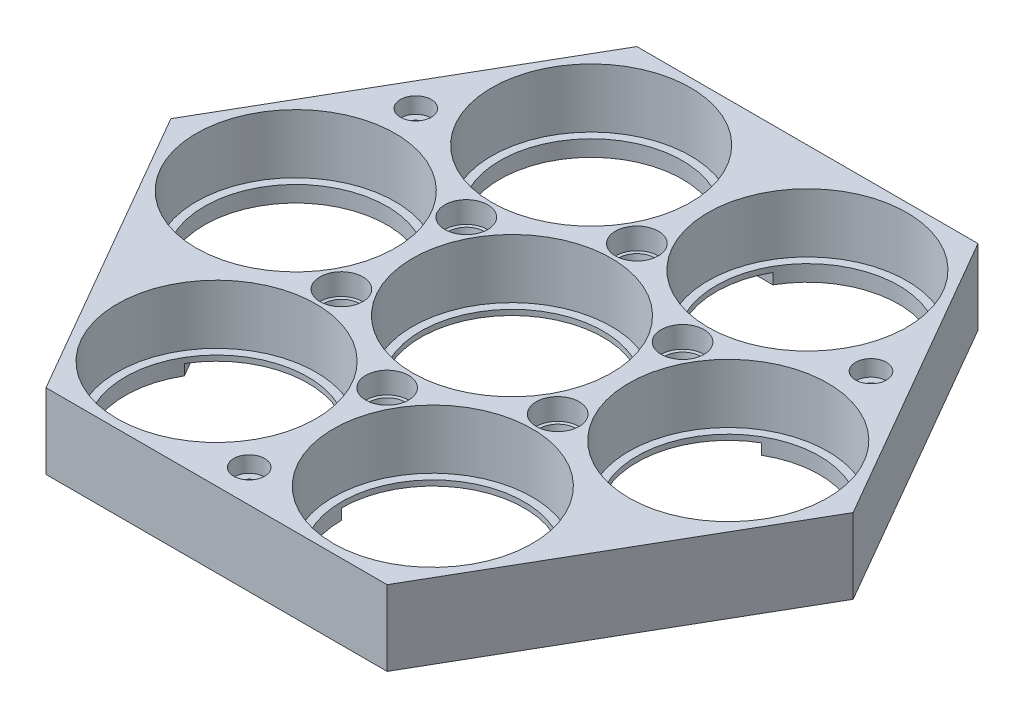
SolidWorks part; units mm, degrees
material "PLA"
ref_plane "Front Plane" through (0, 0, 0) normal (0, 0, 1) x (1, 0, 0)
ref_plane "Top Plane" through (0, 0, 0) normal (0, 1, 0) x (1, 0, 0)
ref_plane "Right Plane" through (0, 0, 0) normal (1, 0, 0) x (0, 0, -1)
sketch "Sketch1" plane through (0, 0, 0) normal (0, 1, 0) x (1, 0, 0)
  line L0 (-23.3, 0) -> (-17, 0) construction
  line L1 (40.3, 0) -> (20.15, 34.9008) construction
  line L2 (20.15, 34.9008) -> (-20.15, 34.9008) construction
  line L3 (-20.15, 34.9008) -> (-40.3, 0) construction
  line L4 (-40.3, 0) -> (-20.15, -34.9008) construction
  line L5 (-20.15, -34.9008) -> (20.15, -34.9008) construction
  line L6 (20.15, -34.9008) -> (40.3, 0) construction
  line L7 (-20.15, 51.9008) -> (-20.15, 55.0508) construction
  line L8 (63.5672, 0) -> (31.7836, 55.0508)
  line L9 (31.7836, 55.0508) -> (-31.7836, 55.0508)
  line L10 (-31.7836, 55.0508) -> (-63.5672, 0)
  line L11 (-63.5672, 0) -> (-31.7836, -55.0508)
  line L12 (-31.7836, -55.0508) -> (31.7836, -55.0508)
  line L13 (31.7836, -55.0508) -> (63.5672, 0)
  line L14 (-20.15, 0) -> (-17, 0)
  circle A0 centre (0, 0) radius 17
  circle A1 centre (0, 0) radius 34.9008 construction
  circle A2 centre (-20.15, 34.9008) radius 17
  circle A3 centre (20.15, 34.9008) radius 17
  circle A4 centre (40.3, 0) radius 17
  circle A5 centre (20.15, -34.9008) radius 17
  circle A6 centre (-20.15, -34.9008) radius 17
  circle A7 centre (-40.3, 0) radius 17
  circle A8 centre (0, 0) radius 55.0508 construction
  dimension "D1" = 34
  dimension "D2" = 6.3
extrude "Boss-Extrude1" add sketch "Sketch1" along normal blind 1 contours L12 L13 L8 L9 L10 L11 A7 A6 A5 A4 A3 A2 A0 region at (46.2189, 0, 26.6845)
sketch "Sketch2" plane through (0, 1, 0) normal (0, 1, 0) x (1, 0, 0)
  line L1 (63.5672, 0) -> (31.7836, 55.0508)
  line L2 (31.7836, 55.0508) -> (-31.7836, 55.0508)
  line L3 (-31.7836, 55.0508) -> (-63.5672, 0)
  line L4 (-63.5672, 0) -> (-31.7836, -55.0508)
  line L5 (-31.7836, -55.0508) -> (31.7836, -55.0508)
  line L6 (31.7836, -55.0508) -> (63.5672, 0)
  circle A0 centre (-40.3, 0) radius 18.525
  circle A1 centre (-20.15, 34.9008) radius 18.525
  circle A2 centre (20.15, 34.9008) radius 18.525
  circle A3 centre (0, 0) radius 18.525
  circle A4 centre (40.3, 0) radius 18.525
  circle A5 centre (20.15, -34.9008) radius 18.525
  circle A6 centre (-20.15, -34.9008) radius 18.525
  circle A7 centre (0, 0) radius 55.0508 construction
  dimension "D1" = 37.05
extrude "Boss-Extrude2" add sketch "Sketch2" along normal blind 11
sketch "Sketch3" plane through (0, 12, 0) normal (0, 1, 0) x (1, 0, 0)
  line L0 (-24.2569, 9.2625) -> (-20.15, 16.3758) construction
  line L1 (-20.15, 16.3758) -> (-16.0431, 9.2625) construction
  line L2 (-16.0431, 9.2625) -> (-24.2569, 9.2625) construction
  circle A0 centre (-20.15, 11.6336) radius 4
  circle A1 centre (20.15, 11.6336) radius 4
  circle A2 centre (0, -23.2672) radius 4
  circle A3 centre (-20.15, -11.6336) radius 4
  circle A4 centre (20.15, -11.6336) radius 4
  circle A5 centre (0, 0) radius 23.2672 construction
  circle A6 centre (-40.3, 0) radius 18.525 construction
  circle A7 centre (-20.15, 34.9008) radius 18.525 construction
  circle A8 centre (0, 0) radius 18.525 construction
  circle A9 centre (0, 23.2672) radius 4
  dimension "D1" = 120
  dimension "D3" = 8
  dimension "D2" = 120
extrude "Cut-Extrude1" cut sketch "Sketch3" against normal blind 4 and the other way through all
extrude "Cut-Extrude2" cut sketch "Sketch3<2>" against normal through all draft 9 contours A0 | A1 | A2 | A3 | A4 | A9 region at (-20.15, 12, -11.6336) region at (20.15, 12, -11.6336) region at (0, 12, 23.2672) region at (-20.15, 12, 11.6336) region at (20.15, 12, 11.6336) region at (0, 12, -23.2672)
sketch "Sketch3<2>" plane through (0, 12, 0) normal (0, 1, 0) x (1, 0, 0) same geometry as "Sketch3"
sketch "Sketch4" plane through (0, 0, 0) normal (0, -1, 0) x (1, 0, 0)
  circle A0 centre (0, -23.2672) radius 4
  circle A1 centre (-20.15, 11.6336) radius 4
  circle A2 centre (20.15, 11.6336) radius 4
  circle A3 centre (0, 0) radius 23.2672 construction
  point P11 (20.15, -11.6336)
  dimension "D1" = 8
sketch "Sketch5" plane through (0, 0, 0) normal (0, -1, 0) x (1, 0, 0)
  line L0 (-63.5672, 0) -> (-31.7836, -55.0508)
  line L1 (-31.7836, -55.0508) -> (-63.5672, 0) construction
  line L3 (-28.65, -20.1784) -> (-31.8, -14.7224)
  line L4 (-63.5672, 0) -> (-57.3, 0)
  line L5 (-5.3512, -43.2672) -> (5.3512, -43.2672)
  line L6 (31.7836, -55.0508) -> (28.65, -49.6233)
  line L7 (-31.7836, -55.0508) -> (31.7836, -55.0508)
  line L8 (31.7836, 55.0508) -> (-31.7836, 55.0508)
  line L9 (-3.15, 34.9008) -> (3.15, 34.9008)
  line L10 (31.7836, 55.0508) -> (28.65, 49.6233)
  line L11 (-34.7949, 26.2679) -> (-40.1461, 16.9993)
  line L12 (-63.5672, 0) -> (-57.3, 0)
  line L13 (-31.7836, 55.0508) -> (-63.5672, 0)
  line L14 (31.7836, -55.0508) -> (63.5672, 0)
  line L15 (31.8, -14.7224) -> (28.65, -20.1784)
  line L16 (31.7836, -55.0508) -> (28.65, -49.6233)
  line L17 (40.1461, 16.9993) -> (34.7949, 26.2679)
  line L18 (31.7836, 55.0508) -> (28.65, 49.6233)
  line L19 (63.5672, 0) -> (31.7836, 55.0508)
  circle A0 centre (-20.15, -34.9008) radius 17 construction
  circle A2 centre (-40.3, 0) radius 17 construction
  arc A3 (-31.8, -14.7224) -> (-57.3, 0) centre (-40.3, 0) cw
  arc A4 (-5.3512, -43.2672) -> (-28.65, -20.1784) centre (-20.15, -34.9008) cw
  circle A5 centre (20.15, -34.9008) radius 17 construction
  arc A6 (5.3512, -43.2672) -> (28.65, -49.6233) centre (20.15, -34.9008) ccw
  circle A7 centre (0, -23.2672) radius 2.0994 construction
  arc A8 (3.15, 34.9008) -> (28.65, 49.6233) centre (20.15, 34.9008) cw
  arc A9 (-34.7949, 26.2679) -> (-3.15, 34.9008) centre (-20.15, 34.9008) cw
  arc A10 (-40.1461, 16.9993) -> (-57.3, 0) centre (-40.3, 0) ccw
  arc A11 (28.65, -20.1784) -> (28.65, -49.6233) centre (20.15, -34.9008) cw
  arc A12 (40.1461, 16.9993) -> (31.8, -14.7224) centre (40.3, 0) cw
  arc A13 (34.7949, 26.2679) -> (28.65, 49.6233) centre (20.15, 34.9008) ccw
  point P55 (0, 0)
  circle M14 centre (-40.3, 0) radius 17
  circle M15 centre (-20.15, 34.9008) radius 17
  circle M16 centre (20.15, 34.9008) radius 17
  circle M17 centre (40.3, 0) radius 17
  circle M18 centre (20.15, -34.9008) radius 17
  circle M19 centre (-20.15, -34.9008) radius 17
  line M20 (31.7836, 55.0508) -> (-31.7836, 55.0508)
  line M21 (-31.7836, 55.0508) -> (-63.5672, 0)
  line M22 (-63.5672, 0) -> (-31.7836, -55.0508)
  line M23 (-31.7836, -55.0508) -> (31.7836, -55.0508)
  line M24 (31.7836, -55.0508) -> (63.5672, 0)
  line M25 (63.5672, 0) -> (31.7836, 55.0508)
  dimension "D1" = 20
  dimension "D2" = 3
extrude "Boss-Extrude3" add sketch "Sketch5" along normal blind 2 contours L11 L9 L10 L4 M15 M16 M20 M21 M14 | L6 L5 L3 L4 M23 M18 M19 M14 M22 | L17 L15 L6 L10 M17 M18 M24 M25 M16 region at (-60.4336, 0, -1.101) region at (-46.7219, 0, 26.9749) region at (31.2171, 0, -51.7595)
sketch "Sketch6" plane through (0, 0, 0) normal (0, 1, 0) x (1, 0, 0)
  line L1 (36.7588, -6.1336) -> (3.5412, -6.1336)
  line L2 (3.5412, -6.1336) -> (-13.0675, -34.9008)
  line L3 (-13.0675, -34.9008) -> (3.5412, -63.668)
  line L4 (3.5412, -63.668) -> (36.7588, -63.668)
  line L5 (36.7588, -63.668) -> (53.3675, -34.9008)
  line L6 (53.3675, -34.9008) -> (36.7588, -6.1336)
  circle A0 centre (20.15, -34.9008) radius 28.7672 construction
  circle A1 centre (20.15, -11.6336) radius 4 construction
  dimension "D1" = 5.5
extrude "Cut-Extrude3" [suppressed] cut sketch "Sketch6" against normal through all both and the other way through all flip side to cut
sketch "Sketch7" plane through (0, 12, 0) normal (0, 1, 0) x (1, 0, 0)
  line L0 (-42.4095, 24.4851) -> (-37.1435, 27.5254) construction
  line L1 (-42.4095, 24.4851) -> (-42.4095, 18.4045) construction
  line L2 (-42.4095, 24.4851) -> (-47.6754, 27.5254) construction
  line L3 (-31.7836, 55.0508) -> (-63.5672, 0) construction
  line L4 (42.4095, 24.4851) -> (42.4095, 18.4045) construction
  line L5 (42.4095, 24.4851) -> (37.1435, 27.5254) construction
  line L6 (42.4095, 24.4851) -> (47.6754, 27.5254) construction
  line L7 (0, -48.9702) -> (-5.266, -45.9299) construction
  line L8 (0, -48.9702) -> (5.266, -45.9299) construction
  line L9 (0, -48.9702) -> (0, -55.0508) construction
  circle A0 centre (-42.4095, 24.4851) radius 2.875
  circle A1 centre (-20.15, 34.9008) radius 18.525 construction
  circle A2 centre (-40.3, 0) radius 18.525 construction
  circle A3 centre (-42.4095, 24.4851) radius 1.55
  circle A4 centre (-20.15, 34.9008) radius 18.525 construction
  circle A5 centre (42.4095, 24.4851) radius 2.875
  circle A6 centre (42.4095, 24.4851) radius 1.55
  circle A7 centre (0, -48.9702) radius 2.875
  circle A8 centre (0, -48.9702) radius 1.55
  point P33 (0, 0)
  dimension "D1" = 5.75
  dimension "D2" = 3.1
  dimension "D3" = 3
extrude "Cut-Extrude4" cut sketch "Sketch7" against normal through all contours A3 | A6 | A8 region at (-42.4095, 12, -24.4851)
extrude "Cut-Extrude5" cut sketch "Sketch7<3>" against normal blind 3 contours A0 A3 | A5 | A7 region at (-45.2031, 12, -24.4851)
sketch "Sketch7<3>" plane through (0, 12, 0) normal (0, 1, 0) x (1, 0, 0) same geometry as "Sketch7"
sketch "Sketch8" plane through (0, 12, 0) normal (0, 1, 0) x (1, 0, 0)
  line L1 (20.15, -34.9008) -> (40.3, 0) construction
  line L2 (40.3, 0) -> (20.15, 34.9008) construction
  line L3 (20.15, 34.9008) -> (-20.15, 34.9008) construction
  line L4 (-20.15, 34.9008) -> (-40.3, 0) construction
  line L5 (-40.3, 0) -> (-20.15, -34.9008) construction
  line L6 (-20.15, -34.9008) -> (20.15, -34.9008) construction
  circle A0 centre (0, 0) radius 34.9008 construction
  dimension "D1" = 69.8016
